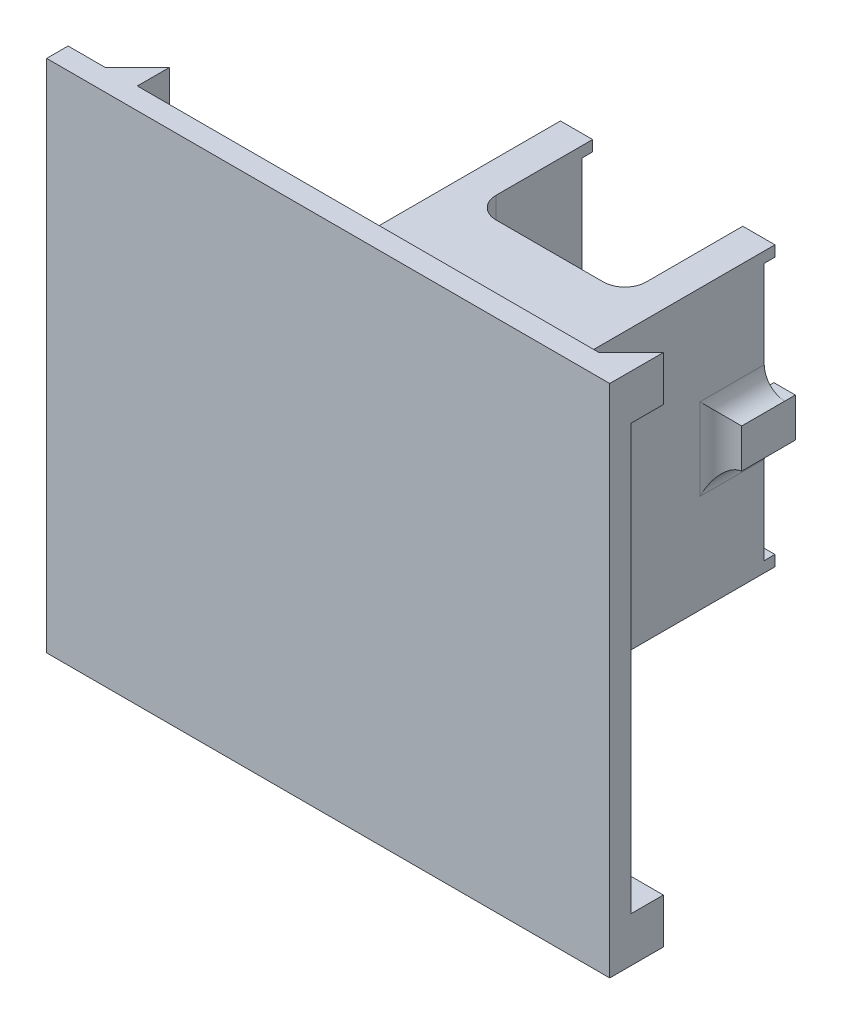
SolidWorks part; units mm, degrees
ref_plane "前视基准面" through (0, 0, 0) normal (0, 0, 1) x (1, 0, 0)
ref_plane "上视基准面" through (0, 0, 0) normal (0, 1, 0) x (1, 0, 0)
ref_plane "右视基准面" through (0, 0, 0) normal (1, 0, 0) x (0, 0, -1)
other "Configuration Table"
sketch "草图1" plane through (0, 0, 0) normal (0, 0, 1) x (1, 0, 0)
  line L0 (-74.7553, 0) -> (91.8672, 0) construction
  line L1 (0, 32.0484) -> (0, -25.9161) construction
  line L2 (-35, 50) -> (35, 50)
  line L3 (-50, 65) -> (50, 65)
  line L4 (-50, 65) -> (-50, -65)
  line L5 (-50, -65) -> (50, -65)
  line L6 (50, 65) -> (50, -65)
  line L7 (-35, 7.5) -> (35, 7.5)
  line L8 (-35, -7.5) -> (35, -7.5)
  line L9 (-35, -50) -> (35, -50)
  line L10 (-35, 50) -> (-35, 7.5)
  line L11 (35, 50) -> (35, 7.5)
  line L12 (-35, -7.5) -> (-35, -50)
  line L13 (0, 0) -> (17.5208, 0) construction
  line L14 (35, -7.5) -> (35, -50)
  dimension "D1" = 130
  dimension "D2" = 100
  dimension "D3" = 15
  dimension "D4" = 15
  dimension "D5" = 15
extrude "凸台-拉伸1" add sketch "草图1" along normal blind 144.5
sketch "草图3" plane through (0, 0, 144.5) normal (0, 0, 1) x (1, 0, 0)
  line L0 (0, 167.568) -> (0, -181.9597) construction
  line L1 (-181.0021, 0) -> (237.2889, 0) construction
  line L2 (50, 65) -> (-50, 65) construction
  line L3 (-50, -65) -> (50, -65) construction
  line L5 (-140, 120) -> (140, 120)
  line L6 (-140, 120) -> (-140, -120)
  line L7 (-140, -120) -> (140, -120)
  line L8 (140, 120) -> (140, -120)
  dimension "D1" = 240
  dimension "D2" = 280
extrude "凸台-拉伸2" add sketch "草图3" against normal blind 10
sketch "草图5" plane through (0, 0, 0) normal (0, 1, 0) x (1, 0, 0)
  line L0 (50, 0) -> (95, 0)
  line L1 (95, 0) -> (95, 70)
  line L2 (95, 70) -> (120, 70)
  line L3 (120, 70) -> (120, -20)
  line L4 (120, -20) -> (50, -20)
  line L5 (50, -134.5) -> (50, 0) construction
  line L6 (50, -20) -> (50, 0)
  line L7 (0, 0) -> (0, -259.1603) construction
  line L8 (50, 0) -> (-50, 0) construction
  line L9 (-50, -20) -> (-50, 0)
  line L10 (-120, -20) -> (-50, -20)
  line L11 (-120, 70) -> (-120, -20)
  line L12 (-95, 70) -> (-120, 70)
  line L13 (-95, 0) -> (-95, 70)
  line L14 (-50, 0) -> (-95, 0)
  line L15 (-50, -134.5) -> (-50, 0) construction
  dimension "D1" = 20
  dimension "D2" = 45
  dimension "D3" = 25
  dimension "D4" = 90
extrude "凸台-拉伸3" add sketch "草图5" along normal mid plane 18.2
sketch "草图6" plane through (0, 0, 0) normal (0, 0, -1) x (-1, 0, 0)
  line L0 (-95, 9.1) -> (-50, 9.1) construction
  line L1 (-49.5, 9.1) -> (-59.5, 9.1)
  line L2 (-49.5, 9.1) -> (-49.5, -9.1)
  line L3 (-49.5, -9.1) -> (-59.5, -9.1)
  line L4 (-59.5, 9.1) -> (-59.5, -9.1)
  line L5 (-95, -9.1) -> (-50, -9.1) construction
  line L6 (0, 82.6485) -> (0, -124.8105) construction
  line L7 (59.5, 9.1) -> (59.5, -9.1)
  line L8 (49.5, -9.1) -> (59.5, -9.1)
  line L9 (49.5, 9.1) -> (49.5, -9.1)
  line L10 (49.5, 9.1) -> (59.5, 9.1)
  dimension "D1" = 99
  dimension "D2" = 10
extrude "凸台-拉伸4" add sketch "草图6" along normal blind 5
sketch "草图12" plane through (0, 65, 0) normal (0, 1, 0) x (1, 0, 0)
  line L0 (-122.7213, -134.5) -> (-107.7213, -119.5)
  line L1 (140, -134.5) -> (-140, -134.5) construction
  line L2 (-107.7213, -119.5) -> (-107.7213, -134.5)
  line L3 (-107.7213, -134.5) -> (-122.7213, -134.5)
  line L4 (107.4787, -134.5) -> (122.4787, -119.5)
  line L8 (122.4787, -119.5) -> (122.4787, -134.5)
  line L9 (122.4787, -134.5) -> (107.4787, -134.5)
  dimension "D1" = 45
  dimension "D2" = 230.2
  dimension "D3" = 15
extrude "凸台-拉伸9" add sketch "草图12" along normal up to surface (55 mm away) from offset 36 up to face at (0, 120, 139.5)
sketch "草图13" plane through (0, 120, 0) normal (0, 1, 0) x (1, 0, 0)
  line L0 (140, -134.5) -> (122.4787, -134.5) construction
  line L1 (122.4787, -119.5) -> (77.4787, -119.5)
  line L2 (122.4787, -119.5) -> (122.4787, -134.5)
  line L3 (122.4787, -134.5) -> (77.4787, -134.5)
  line L4 (77.4787, -119.5) -> (77.4787, -134.5)
  line L5 (-122.7213, -134.5) -> (-140, -134.5) construction
  line L6 (-107.7213, -119.5) -> (-107.7213, -134.5)
  line L7 (-152.7213, -134.5) -> (-107.7213, -134.5)
  line L8 (-152.7213, -119.5) -> (-152.7213, -134.5)
  line L9 (-152.7213, -119.5) -> (-107.7213, -119.5)
  dimension "D1" = 45
extrude "凸台-拉伸10" add sketch "草图13" along normal blind 4 and the other way blind 2 from surface starting at face at (117.4787, 101, 129.5)
mirror "镜向4" about plane through (0, 0, 0) normal (0, 1, 0) of bodies 117
fillet "圆角4" radius 10 6 edges at (-50, 0, 20) (50, 0, 20) (-50, -9.1, 10) (50, -9.1, 10) (50, 9.1, 10) (-50, 9.1, 10)
fillet "圆角6" radius 5 4 edges at (0, 65, 134.5) (50, 0, 134.5) (0, -65, 134.5) (-50, 0, 134.5)
sketch "草图14" plane through (0, 0, 0) normal (0, 0, -1) x (-1, 0, 0)
  line L0 (59.5, -9.1) -> (59.5, 9.1) construction
  line L1 (59.5, 11.2754) -> (127.7356, 11.2754)
  line L2 (59.5, 11.2754) -> (59.5, -23.7818)
  line L3 (59.5, -23.7818) -> (127.7356, -23.7818)
  line L4 (127.7356, 11.2754) -> (127.7356, -23.7818)
  line L5 (-59.5, 19.1084) -> (-135.1439, 19.1084)
  line L6 (-59.5, 19.1084) -> (-59.5, -23.7818)
  line L7 (-59.5, -23.7818) -> (-135.1439, -23.7818)
  line L8 (-135.1439, 19.1084) -> (-135.1439, -23.7818)
  line L10 (-59.5, 9.1) -> (-59.5, -9.1) construction
extrude "切除-拉伸1" cut sketch "草图14" against normal up to next and the other way through all
sketch "草图15" plane through (0, 120, 0) normal (0, 1, 0) x (1, 0, 0)
  line L0 (122.4787, -119.5) -> (77.4787, -119.5) construction
  line L1 (122.4787, -134.5) -> (155.8244, -134.5)
  line L2 (122.4787, -134.5) -> (122.4787, -144.77)
  line L3 (122.4787, -144.77) -> (155.8244, -144.77)
  line L4 (155.8244, -134.5) -> (155.8244, -144.77)
  line L5 (-140, -134.5) -> (-168.4496, -134.5)
  line L6 (-140, -134.5) -> (-140, -92.9194)
  line L7 (-140, -92.9194) -> (-168.4496, -92.9194)
  line L8 (-168.4496, -134.5) -> (-168.4496, -92.9194)
  line L9 (77.4787, -134.5) -> (92.4787, -134.5)
  line L10 (77.4787, -134.5) -> (77.4787, -119.5)
  line L11 (77.4787, -119.5) -> (92.4787, -119.5)
  line L12 (92.4787, -134.5) -> (92.4787, -119.5)
  dimension "D1" = 15
extrude "切除-拉伸2" cut sketch "草图15" against normal through all
sketch "草图16" plane through (0, 0, 0) normal (0, 0, -1) x (-1, 0, 0)
  line L0 (0, 94.3868) -> (0, -138.0446) construction
  line L1 (-35, 81.4751) -> (35, 81.4751)
  line L2 (-35, 81.4751) -> (-35, -80.8285)
  line L3 (-35, -80.8285) -> (35, -80.8285)
  line L4 (35, 81.4751) -> (35, -80.8285)
  line L5 (35, 50) -> (35, 7.5) construction
extrude "切除-拉伸3" cut sketch "草图16" against normal blind 50
sketch "草图17" plane through (0, 0, 0) normal (0, 0, -1) x (-1, 0, 0)
  line L0 (-35, -65) -> (-35, 65) construction
  line L1 (-50, 65) -> (-35, 65)
  line L2 (-50, 65) -> (-50, 60)
  line L3 (-50, 60) -> (-35, 60)
  line L4 (-35, 65) -> (-35, 60)
  line L5 (-145.4821, 0) -> (195.4442, 0) construction
  line L6 (0, 137.8055) -> (0, -210.4539) construction
  line L7 (35, 65) -> (35, 60)
  line L8 (50, 60) -> (35, 60)
  line L9 (50, 65) -> (50, 60)
  line L10 (50, 65) -> (35, 65)
  line L11 (50, -65) -> (35, -65)
  line L12 (50, -65) -> (50, -60)
  line L13 (50, -60) -> (35, -60)
  line L14 (35, -65) -> (35, -60)
  line L15 (-35, -65) -> (-35, -60)
  line L16 (-50, -60) -> (-35, -60)
  line L17 (-50, -65) -> (-50, -60)
  line L18 (-50, -65) -> (-35, -65)
  dimension "D1" = 5
extrude "凸台-拉伸11" add sketch "草图17" along normal blind 5
fillet "圆角7" radius 10 6 edges at (-35, -57.5, 50) (-35, 0, 50) (-35, 57.5, 50) (35, -57.5, 50) (35, 0, 50) (35, 57.5, 50)
